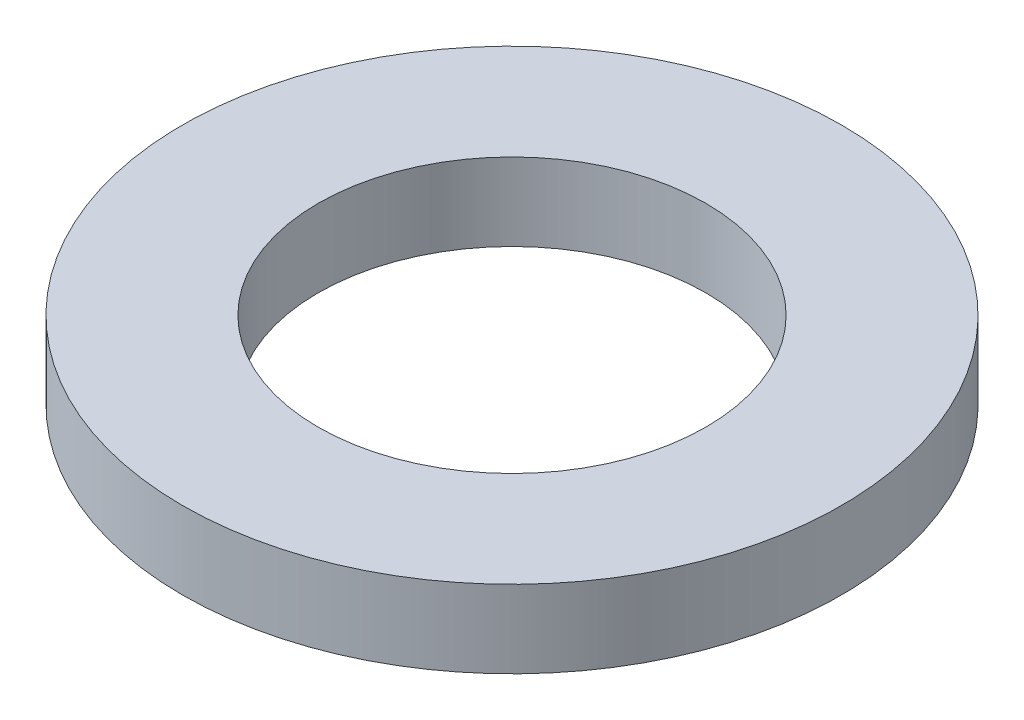
SolidWorks part; units mm, degrees
ref_plane "Front Plane" through (0, 0, 0) normal (0, 0, 1) x (1, 0, 0)
ref_plane "Top Plane" through (0, 0, 0) normal (0, 1, 0) x (1, 0, 0)
ref_plane "Right Plane" through (0, 0, 0) normal (1, 0, 0) x (0, 0, -1)
sketch "Sketch1" plane through (0, 0, 0) normal (0, 1, 0) x (1, 0, 0)
  circle A0 centre (0, 0) radius 85
  dimension "FLANGE_OD" = 170
extrude "Boss-Extrude1" add sketch "Sketch1" along normal blind 20
sketch "Sketch2" plane through (0, 0, 0) normal (0, 1, 0) x (1, 0, 0)
  circle A0 centre (0, 0) radius 50
  dimension "BORE_D" = 100
extrude "Cut-Extrude1" cut sketch "Sketch2" along normal through all
sketch "Sketch3" plane through (0, 20, 0) normal (0, 1, 0) x (1, 0, 0)
  circle A0 centre (0, 0) radius 29.9375 construction
  circle A1 centre (-29.9375, 0) radius 2.1804
  dimension "BOLT_D" = 4.3609
  dimension "BOLT_PCD" = 59.875
extrude "Cut-Extrude2" cut sketch "Sketch3" against normal blind 16.4431 rebuild error yes
pattern_circular "CirPattern1" count 6 over 360 rebuild error yes
